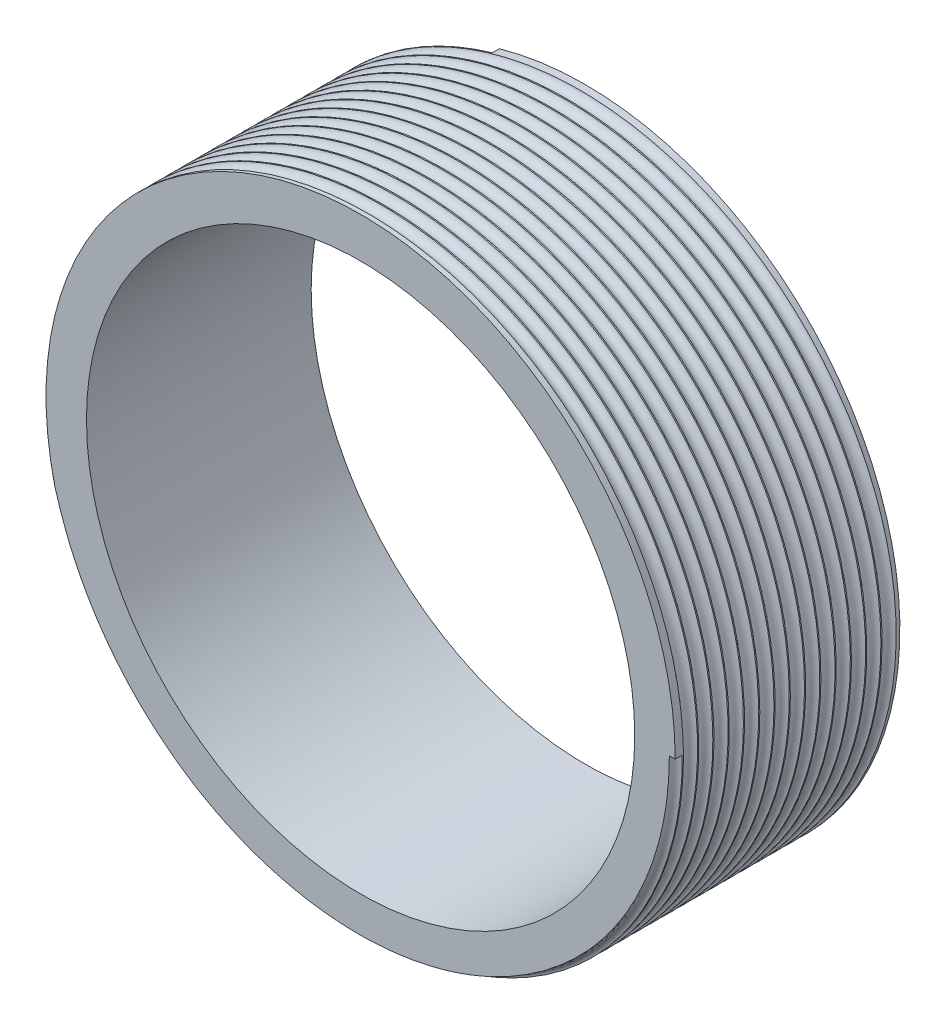
SolidWorks part; units mm, degrees
material "1.0116 (S235J2G3)"
ref_plane "Front Plane" through (0, 0, 0) normal (0, 0, 1) x (1, 0, 0)
ref_plane "Top Plane" through (0, 0, 0) normal (0, 1, 0) x (1, 0, 0)
ref_plane "Right Plane" through (0, 0, 0) normal (1, 0, 0) x (0, 0, -1)
sketch "Sketch1" plane through (0, 0, 0) normal (0, 0, 1) x (1, 0, 0)
  circle A0 centre (0, 0) radius 70
  circle A1 centre (0, 0) radius 61
  dimension "D1" = 140
  dimension "D2" = 9
extrude "Boss-Extrude1" add sketch "Sketch1" along normal mid plane 50
ref_plane "Plane1" through (0, 0, 25) normal (0, 0, 1) x (1, 0, 0)
sketch "Sketch2" plane through (0, 0, 25) normal (0, 0, 1) x (1, 0, 0)
  circle A0 centre (0, 0) radius 70.3
  dimension "D1" = 140.6
curve "Helix/Spiral1" pitch 3.4 height 50 turns 14.7059
sweep "Cut-Sweep1" cut path "Helix/Spiral1" parameters "D3"=3.2
sketch "Sketch9" plane through (0.1851, 0.0527, -0.0015) normal (-0.9618, -0.2737, 0.0077) x (-0.2735, 0.9617, 0.0205)
  circle A0 centre (70.2341, 22.2083) radius 1.6
  dimension "D1" = 3.2
extrude "Cut-Extrude1" [suppressed] cut sketch "Sketch9" against normal blind 50
sketch "Sketch10" plane through (0, 0.1924, 0.0015) normal (0, -1, -0.0077) x (1, 0, 0)
  circle A0 centre (70.3, 21.9993) radius 1.6
  dimension "D1" = 3.2
extrude "Cut-Extrude2" [suppressed] cut sketch "Sketch10" against normal blind 50
